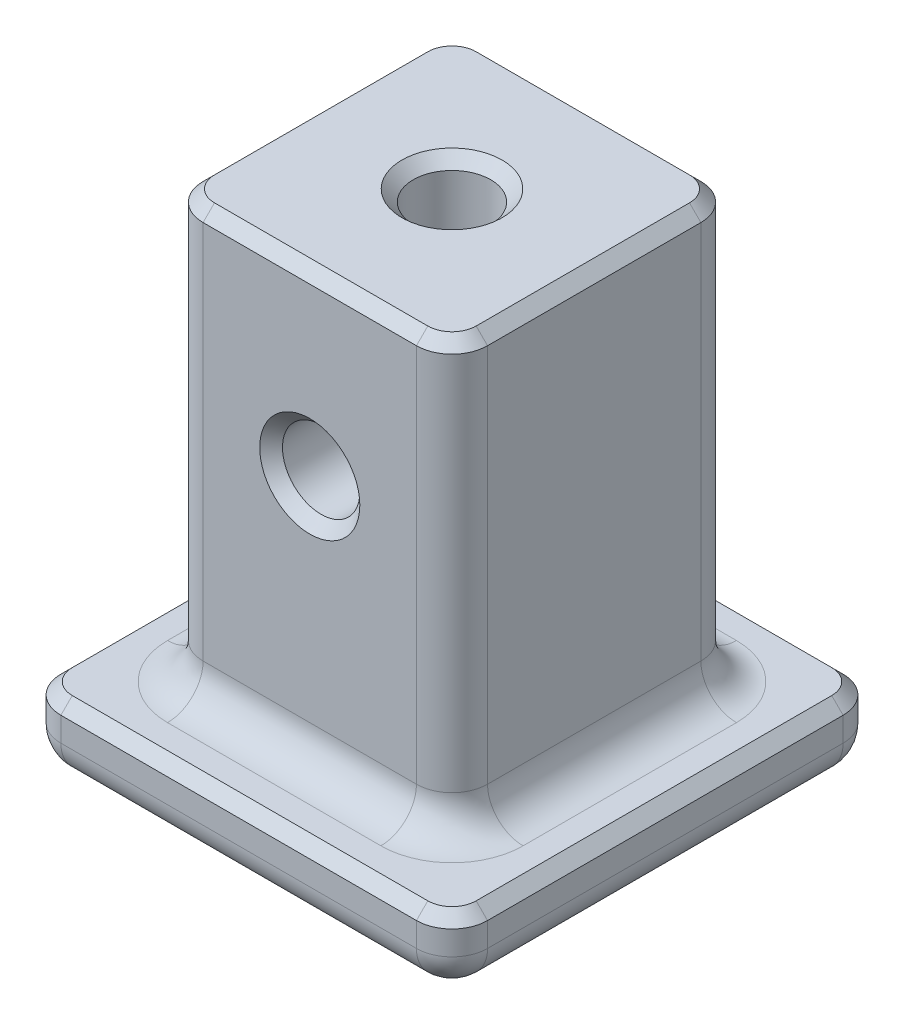
SolidWorks part; units mm, degrees
ref_plane "Front Plane" through (0, 0, 0) normal (0, 0, 1) x (1, 0, 0)
ref_plane "Top Plane" through (0, 0, 0) normal (0, 1, 0) x (1, 0, 0)
ref_plane "Right Plane" through (0, 0, 0) normal (1, 0, 0) x (0, 0, -1)
sketch "Sketch1" plane through (0, 0, 0) normal (0, 1, 0) x (1, 0, 0)
  line L1 (-9.525, -9.525) -> (9.525, -9.525)
  line L2 (-9.525, -9.525) -> (-9.525, 9.525)
  line L3 (-9.525, 9.525) -> (9.525, 9.525)
  line L4 (9.525, -9.525) -> (9.525, 9.525)
  line L5 (-9.525, -9.525) -> (9.525, 9.525) construction
  line L6 (-9.525, 9.525) -> (9.525, -9.525) construction
  point P0 (0, 0)
  dimension "D1" = 19.05
extrude "Boss-Extrude1" add sketch "Sketch1" along normal blind 22.225
sketch "Sketch2" plane through (0, 22.225, 0) normal (0, 1, 0) x (1, 0, 0)
  line L1 (-6.35, -6.35) -> (6.35, -6.35)
  line L2 (-6.35, -6.35) -> (-6.35, 6.35)
  line L3 (-6.35, 6.35) -> (6.35, 6.35)
  line L4 (6.35, -6.35) -> (6.35, 6.35)
  line L5 (-6.35, -6.35) -> (6.35, 6.35) construction
  line L6 (-6.35, 6.35) -> (6.35, -6.35) construction
  point P0 (0, 0)
  dimension "D1" = 12.7
extrude "Cut-Extrude1" cut sketch "Sketch2" against normal blind 19.05 flip side to cut
hole_wizard "#8-32 Tapped Hole2" positions "Sketch5" profile "Sketch6" tap size "#8-32" standard "ANSI Inch" end condition through all
sketch "Sketch5" plane through (0, 0, 0) normal (0, -1, 0) x (-1, 0, 0)
  point P0 (0, 0)
sketch "Sketch6" plane through (0, 0, 0) normal (1, 0, 0) x (0, 0, -1)
  line L0 (0, 0) -> (0, 22.225)
  line L1 (0, 22.225) -> (1.7272, 22.225)
  line L2 (1.7272, 22.225) -> (1.7272, 0)
  line L5 (1.7272, 0) -> (0, 0)
  line L11 (0, -6.35) -> (0, 107.95) construction
  dimension "Thru Tap Drill Dia." = 3.4544
  dimension "Thru Tap Drill Depth" = 22.225
cosmetic thread "Hole Thread2" parameters "D2"=4.1656
hole_wizard "#8-32 Tapped Hole1" positions "Sketch3" profile "Sketch4" tap size "#8-32" standard "ANSI Inch" end condition through all
sketch "Sketch3" plane through (0, 0, 6.35) normal (0, 0, 1) x (1, 0, 0)
  line L0 (-9.525, 3.175) -> (9.525, 3.175) construction
  point P0 (0, 14.2875)
  dimension "D1" = 11.1125
sketch "Sketch4" plane through (0, 14.2875, 6.35) normal (1, 0, 0) x (0, -1, 0)
  line L0 (0, 0) -> (0, 15.875)
  line L1 (0, 15.875) -> (1.7272, 15.875)
  line L2 (1.7272, 15.875) -> (1.7272, 0)
  line L5 (1.7272, 0) -> (0, 0)
  line L11 (0, -6.35) -> (0, 107.95) construction
  dimension "Thru Tap Drill Dia." = 3.4544
  dimension "Thru Tap Drill Depth" = 15.875
cosmetic thread "Hole Thread1" parameters "D2"=4.1656
fillet "Fillet1" radius 1.5875 16 edges at (-9.525, 0, 0) (0, 0, 9.525) (9.525, 0, 0) (0, 0, -9.525) (9.525, 1.5875, 9.525) (-9.525, 1.5875, 9.525) (-9.525, 1.5875, -9.525) (9.525, 1.5875, -9.525) (0, 3.175, 6.35) (6.35, 3.175, 0) (0, 3.175, -6.35) (-6.35, 3.175, 0) (6.35, 12.7, 6.35) (-6.35, 12.7, 6.35) (6.35, 12.7, -6.35) (-6.35, 12.7, -6.35)
chamfer "Chamfer1" distance 0.508 angle 45 20 edges at (0, 3.175, -9.525) (-9.06, 3.175, -9.06) (9.06, 3.175, -9.06) (-9.525, 3.175, 0) (9.525, 3.175, 0) (-9.06, 3.175, 9.06) (9.06, 3.175, 9.06) (0, 3.175, 9.525) (0, 22.225, -6.35) (-5.885, 22.225, -5.885) (5.885, 22.225, -5.885) (-6.35, 22.225, 0) (6.35, 22.225, 0) (-5.885, 22.225, 5.885) (5.885, 22.225, 5.885) (0, 22.225, 6.35) (-1.7272, 14.2875, -6.35) (1.7272, 14.2875, 6.35) (0, 22.225, -1.7272) (0, 0, -1.7272)
